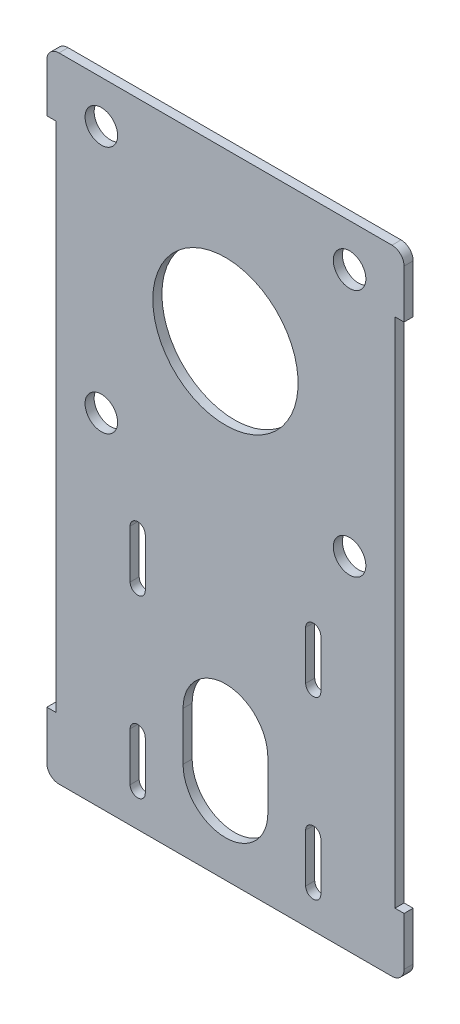
SolidWorks part; units mm, degrees
ref_plane "Front Plane" through (0, 0, 0) normal (0, 0, 1) x (1, 0, 0)
ref_plane "Top Plane" through (0, 0, 0) normal (0, 1, 0) x (1, 0, 0)
ref_plane "Right Plane" through (0, 0, 0) normal (1, 0, 0) x (0, 0, -1)
sketch "Sketch1" plane through (0, 0, 0) normal (0, 0, 1) x (1, 0, 0)
  line L0 (0, 87.3125) -> (0, -244.7446) construction
  line L1 (93.6625, 87.3125) -> (-93.6625, 87.3125)
  line L2 (93.6625, 87.3125) -> (93.6625, -244.7446)
  line L3 (93.6625, -244.7446) -> (-93.6625, -244.7446)
  line L4 (-93.6625, 87.3125) -> (-93.6625, -244.7446)
  line L5 (65.0875, 80.9625) -> (-65.0875, 80.9625) construction
  line L6 (-80.9625, 65.0875) -> (-80.9625, -65.0875) construction
  arc A0 (-47.7494, -219.9794) -> (47.7494, -219.9794) centre (0, -23.368) ccw construction
  point P11 (0, -225.6946)
  dimension "D1" = 6.35
  dimension "D2" = 12.7
  dimension "D3" = 19.05
extrude "Extrude1" add sketch "Sketch1" against normal blind 4.7625
sketch "Sketch2" plane through (0, 0, 0) normal (0, 0, 1) x (1, 0, 0)
  line L0 (22.225, -190.5) -> (-22.225, -190.5) construction
  line L1 (-22.225, -203.2) -> (-22.225, -177.8)
  line L2 (22.225, -203.2) -> (22.225, -177.8)
  line L3 (46.0248, -134.3152) -> (46.0248, -108.9152) construction
  line L4 (-46.0248, -134.3152) -> (-46.0248, -108.9152) construction
  line L5 (-46.0248, -200.9648) -> (-46.0248, -226.3648) construction
  line L6 (46.0248, -200.9648) -> (46.0248, -226.3648) construction
  line L7 (49.9935, -108.9152) -> (49.9935, -134.3152)
  line L8 (42.0561, -108.9152) -> (42.0561, -134.3152)
  line L9 (-42.056, -108.9152) -> (-42.056, -134.3152)
  line L10 (-49.9935, -108.9152) -> (-49.9935, -134.3152)
  line L11 (49.9935, -200.9648) -> (49.9935, -226.3648)
  line L12 (42.0561, -226.3648) -> (42.056, -200.9648)
  line L13 (-42.0561, -200.9648) -> (-42.0561, -226.3648)
  line L14 (-49.9936, -200.9648) -> (-49.9935, -226.3648)
  arc A0 (2.3812, -199.7225) -> (-2.3813, -199.7225) centre (0, -190.5) ccw construction
  arc A1 (22.225, -177.8) -> (-22.225, -177.8) centre (0, -177.8) ccw
  arc A2 (-22.225, -203.2) -> (22.225, -203.2) centre (0, -203.2) ccw
  arc A3 (49.9935, -108.9152) -> (42.0561, -108.9152) centre (46.0248, -108.9152) ccw
  arc A4 (42.0561, -134.3152) -> (49.9935, -134.3152) centre (46.0248, -134.3152) ccw
  arc A5 (-49.9935, -134.3152) -> (-42.056, -134.3152) centre (-46.0248, -134.3152) ccw
  arc A6 (-42.056, -108.9152) -> (-49.9935, -108.9152) centre (-46.0248, -108.9152) ccw
  arc A7 (-42.0561, -200.9648) -> (-49.9936, -200.9648) centre (-46.0248, -200.9648) ccw
  arc A8 (-49.9935, -226.3648) -> (-42.0561, -226.3648) centre (-46.0248, -226.3648) ccw
  arc A9 (49.9935, -200.9648) -> (42.056, -200.9648) centre (46.0248, -200.9648) ccw
  arc A10 (49.9935, -226.3648) -> (42.0561, -226.3648) centre (46.0248, -226.3648) cw
  point P0 (0, -190.5)
  point P12 (46.0248, -121.6152)
  point P16 (-46.0248, -121.6152)
  point P20 (-46.0248, -213.6648)
  point P21 (46.0248, -213.6648)
  dimension "D3" = 7.9375
  dimension "D1" = 25.4
  dimension "D2" = 44.45
extrude "Cut-Extrude1" cut sketch "Sketch2" against normal up to next
sketch "Sketch3" plane through (0, 0, 0) normal (0, 0, -1) x (-1, 0, 0)
  circle A0 centre (0, 0) radius 38.1
  circle A1 centre (65.0875, 65.0875) radius 8.5328
  circle A2 centre (-65.0875, 65.0875) radius 8.5328
  circle A3 centre (-65.0875, -65.0875) radius 8.5328
  circle A4 centre (65.0875, -65.0875) radius 8.5328
  circle A5 centre (65.0875, -65.0875) radius 8.5328 construction
  circle A6 centre (65.0875, 65.0875) radius 8.5328 construction
  circle A7 centre (-65.0875, 65.0875) radius 8.5328 construction
  circle A8 centre (-65.0875, -65.0875) radius 8.5328 construction
  dimension "D1" = 76.2
extrude "Cut-Extrude2" cut sketch "Sketch3" along normal up to next
sketch "Sketch4" plane through (0, 0, -4.7625) normal (0, 0, -1) x (-1, 0, 0)
  line L1 (-88.9, -212.9946) -> (-93.6625, -212.9946)
  line L2 (-88.9, -212.9946) -> (-88.9, 55.5625)
  line L3 (-88.9, 55.5625) -> (-93.6625, 55.5625)
  line L4 (-93.6625, -212.9946) -> (-93.6625, 55.5625)
extrude "Cut-Extrude3" cut sketch "Sketch4" against normal up to next
mirror "Mirror1" about plane through (0, 0, 0) normal (1, 0, 0) of "Cut-Extrude3"
fillet "Fillet1" radius 6.35 4 edges at (-93.6625, 87.3125, -2.3813) (-93.6625, -244.7446, -2.3813) (93.6625, -244.7446, -2.3813) (93.6625, 87.3125, -2.3813)
